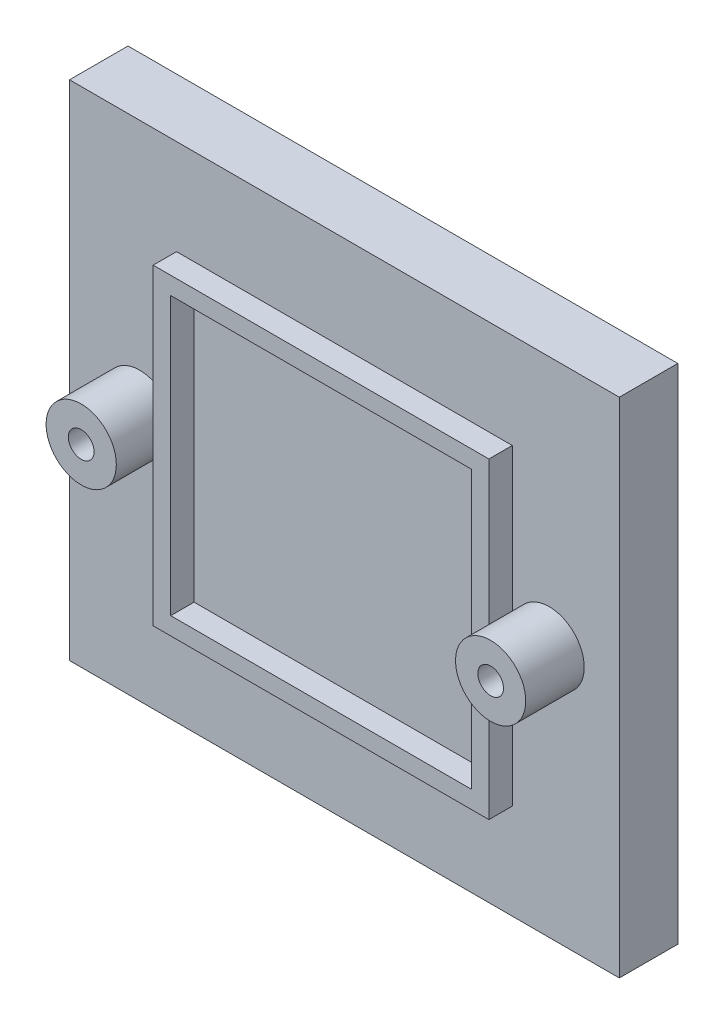
SolidWorks part; units mm, degrees
ref_plane "前视基准面" through (0, 0, 0) normal (0, 0, 1) x (1, 0, 0)
ref_plane "上视基准面" through (0, 0, 0) normal (0, 1, 0) x (1, 0, 0)
ref_plane "右视基准面" through (0, 0, 0) normal (1, 0, 0) x (0, 0, -1)
sketch "草图1" plane through (0, 0, 0) normal (0, 0, 1) x (1, 0, 0)
  line L0 (-14.35, 13.35) -> (14.35, 13.35)
  line L1 (-12.85, 11.85) -> (12.85, 11.85)
  line L2 (-12.85, 11.85) -> (-12.85, -11.85)
  line L3 (-12.85, -11.85) -> (12.85, -11.85)
  line L4 (12.85, 11.85) -> (12.85, -11.85)
  line L5 (0, -11.85) -> (0, 11.85) construction
  line L6 (-12.85, 0) -> (12.85, 0) construction
  line L7 (14.35, 13.35) -> (14.35, -13.35)
  line L8 (-14.35, -13.35) -> (14.35, -13.35)
  line L9 (-14.35, 13.35) -> (-14.35, -13.35)
  line L10 (12.85, 0) -> (17.5, 0) construction
  line L11 (0, -11.85) -> (0, -17.5) construction
  line L13 (-23.5, 21.5) -> (23.5, 21.5)
  line L14 (-23.5, 21.5) -> (-23.5, -21.5)
  line L15 (-23.5, -21.5) -> (23.5, -21.5)
  line L16 (23.5, 21.5) -> (23.5, -21.5)
  line L17 (0, -21.5) -> (0, 21.5) construction
  line L18 (-23.5, 0) -> (23.5, 0) construction
  circle A0 centre (17.5, 0) radius 1.1
  circle A1 centre (17.5, 0) radius 3
  circle A2 centre (-17.5, 0) radius 3
  circle A3 centre (-17.5, 0) radius 1.1
  point P0 (0, 0)
  point P26 (0, 0)
  dimension "D5" = 2.2
  dimension "D1" = 25.7
  dimension "D2" = 23.7
  dimension "D4" = 17.5
  dimension "D10" = 47
  dimension "D11" = 43
  dimension "D3" = 1.5
  dimension "D6" = 1.9
extrude "凸台-拉伸2" add sketch "草图1" along normal blind 2 contours L0 L9 L8 L7 L1 L4 L3 L2 region at (0, 12.958, 0)
extrude "凸台-拉伸5" add sketch "草图1<7>" along normal blind 5 separate body contours A2 A3 | A1 A0 region at (14.5849, 0, 0) region at (-20.4151, 0, 0)
sketch "草图1<7>" plane through (0, 0, 0) normal (0, 0, 1) x (1, 0, 0) same geometry as "草图1"
extrude "凸台-拉伸6" add sketch "草图1<8>" against normal blind 5 contours L13 L16 L15 L14
sketch "草图1<8>" plane through (0, 0, 0) normal (0, 0, 1) x (1, 0, 0) same geometry as "草图1"
